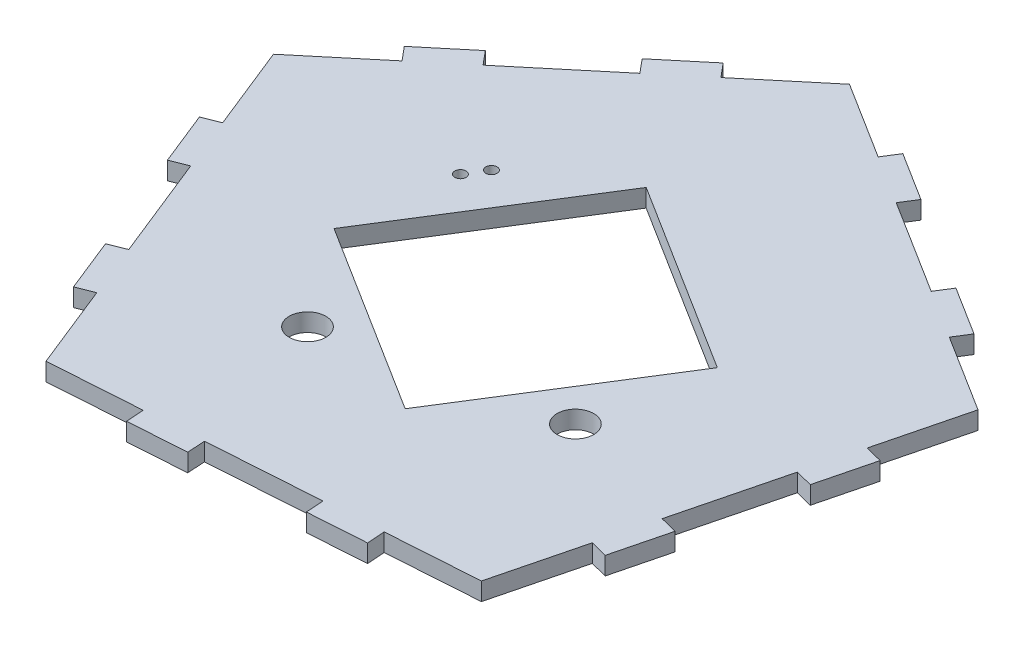
SolidWorks part; units mm, degrees
ref_plane "Front Plane" through (0, 0, 0) normal (0, 0, 1) x (1, 0, 0)
ref_plane "Top Plane" through (0, 0, 0) normal (0, 1, 0) x (1, 0, 0)
ref_plane "Right Plane" through (0, 0, 0) normal (1, 0, 0) x (0, 0, -1)
sketch "Sketch1" plane through (0, 0, 0) normal (0, 1, 0) x (1, 0, 0)
  line L1 (-59.9258, 15.1181) -> (-32.8962, -52.3211)
  line L2 (-32.8962, -52.3211) -> (39.5948, -47.4543)
  line L3 (39.5948, -47.4543) -> (57.3672, 22.9927)
  line L4 (57.3672, 22.9927) -> (-4.14, 61.6646)
  line L5 (-4.14, 61.6646) -> (-59.9258, 15.1181)
  circle A0 centre (0, 0) radius 50 construction
  dimension "D1" = 100
extrude "Boss-Extrude1" add sketch "Sketch1" along normal blind 3.18
ref_axis "Axis" through (0, 3.339, 0) along (0, -1, 0)
sketch "Axis Check" plane through (0, 3.18, 0) normal (0, 1, 0) x (1, 0, 0)
  line L0 (3.3493, -49.8877) -> (-4.14, 61.6646) construction
  line L1 (-32.8962, -52.3211) -> (39.5948, -47.4543) construction
  line L2 (57.3672, 22.9927) -> (-46.411, -18.6015) construction
  line L3 (-59.9258, 15.1181) -> (-32.8962, -52.3211) construction
  line L4 (-32.0329, 38.3913) -> (39.5948, -47.4543) construction
  line L5 (-4.14, 61.6646) -> (-59.9258, 15.1181) construction
  line L6 (-59.9258, 15.1181) -> (48.481, -12.2308) construction
  line L7 (39.5948, -47.4543) -> (57.3672, 22.9927) construction
  line L8 (-32.8962, -52.3211) -> (26.6136, 42.3287) construction
  line L9 (57.3672, 22.9927) -> (-4.14, 61.6646) construction
sketch "Sketch2" plane through (0, 0, 0) normal (0, -1, 0) x (1, 0, 0)
  line L0 (-53.8107, 0.1392) -> (-50.859, -1.0438)
  line L1 (-53.8107, 0.1392) -> (-50.1723, 9.2172)
  line L2 (-50.859, -1.0438) -> (-47.2205, 8.0342)
  line L3 (-50.1723, 9.2172) -> (-47.2205, 8.0342)
  line L4 (-59.9258, -15.1181) -> (-32.8962, 52.3211) construction
  line L5 (-42.6498, 27.9858) -> (-39.0113, 37.0638)
  line L6 (-42.6498, 27.9858) -> (-39.6981, 26.8028)
  line L7 (-39.0113, 37.0638) -> (-36.0596, 35.8808)
  line L8 (-39.6981, 26.8028) -> (-36.0596, 35.8808)
  line L9 (-46.411, 18.6015) -> (-19.2439, 7.7129) construction
  line L10 (-40.8306, 32.5248) -> (-37.8788, 31.3418) construction
  dimension "D1" = 3.18
  dimension "D2" = 9.78
  dimension "D3" = 10.11
extrude "Cut F" [suppressed] cut sketch "Sketch2" against normal through all
sketch "Sketch4" plane through (0, 3.18, 0) normal (0, 1, 0) x (1, 0, 0)
  line L9 (26.6136, 42.3287) -> (-26.6136, -42.3287) construction
  line L10 (57.3672, 22.9927) -> (-4.14, 61.6646) construction
  line L11 (-27.7286, -6.3206) -> (-6.3206, 27.7286)
  line L12 (-27.7286, -6.3206) -> (6.3206, -27.7286)
  line L13 (-6.3206, 27.7286) -> (27.7286, 6.3206)
  line L14 (6.3206, -27.7286) -> (27.7286, 6.3206)
  line L15 (-27.7286, -6.3206) -> (27.7286, 6.3206) construction
  line L16 (-6.3206, 27.7286) -> (6.3206, -27.7286) construction
  line L20 (0, 0) -> (39.0006, -24.5211) construction
  circle A0 centre (-14.9622, -23.7972) radius 3.25
  circle A1 centre (23.7972, -14.9622) radius 3.25
  point P5 (0, 0)
  point P6 (-14.9622, -23.7972)
  dimension "D3" = 6.5
  dimension "D1" = 40.22
  dimension "D2" = 40.22
  dimension "D4" = 8
  dimension "D5" = 8
extrude "Top Cut" cut sketch "Sketch4" against normal blind 10
sketch "Sketch7" plane through (0, 3.18, 0) normal (0, 1, 0) x (1, 0, 0)
  line L0 (0, 0) -> (26.6136, 42.3287) construction
  line L1 (57.3672, 22.9927) -> (-4.14, 61.6646) construction
  line L2 (1.0645, 1.6931) -> (-22.7326, 16.6553) construction
  line L3 (-6.1086, 1.4782) -> (-24.8617, 13.269) construction
  line L5 (-6.3206, 27.7286) -> (-27.7286, -6.3206) construction
  circle A0 centre (-22.7326, 16.6553) radius 1
  circle A1 centre (-24.8617, 13.269) radius 1
  dimension "D5" = 2
  dimension "D1" = 4
  dimension "D2" = 2
  dimension "D3" = 8
  dimension "D4" = 8
extrude "Top Cut 2" cut sketch "Sketch7" against normal through all
sketch "Sketch8" [suppressed] plane through (0, 3.18, 0) normal (0, 1, 0) x (1, 0, 0)
  line L0 (3.3493, -49.8877) -> (-4.14, 61.6646) construction
  line L5 (-32.8962, -52.3211) -> (39.5948, -47.4543) construction
  line L6 (-17.9455, -31.2723) -> (21.9647, -28.5929)
  line L11 (-17.9455, -31.2723) -> (-21.9647, 28.5929)
  line L12 (21.9647, -28.5929) -> (17.9455, 31.2723)
  line L13 (-21.9647, 28.5929) -> (17.9455, 31.2723)
  point P4 (1.4955, -22.2759)
  dimension "D1" = 60
  dimension "D2" = 40
  dimension "D3" = 20
extrude "Bottom Cut" [suppressed] cut sketch "Sketch8" against normal blind 10
sketch "Sketch9" [suppressed] plane through (0, 3.18, 0) normal (0, 1, 0) x (1, 0, 0)
  line L0 (19.9551, 1.3397) -> (-19.9551, -1.3397) construction
  line L1 (21.9647, -28.5929) -> (17.9455, 31.2723) construction
  line L2 (-21.9647, 28.5929) -> (-17.9455, -31.2723) construction
  line L3 (-19.9551, -1.3397) -> (-44.4689, -2.9855) construction
  line L4 (19.9551, 1.3397) -> (43.083, 2.8925) construction
  line L5 (-32.8962, -52.3211) -> (39.5948, -47.4543) construction
  line L6 (-29.6051, -6.8886) -> (-32.7779, -7.1016)
  line L7 (-29.6051, -6.8886) -> (-30.2602, 2.8694)
  line L8 (-30.2602, 2.8694) -> (-33.433, 2.6564)
  line L9 (-32.7779, -7.1016) -> (-33.433, 2.6564)
  line L10 (-29.6051, -6.8886) -> (-33.433, 2.6564) construction
  line L11 (-30.2602, 2.8694) -> (-32.7779, -7.1016) construction
  line L12 (33.433, -2.6564) -> (30.2602, -2.8694)
  line L13 (33.433, -2.6564) -> (32.7779, 7.1016)
  line L14 (32.7779, 7.1016) -> (29.6051, 6.8886)
  line L15 (30.2602, -2.8694) -> (29.6051, 6.8886)
  line L16 (33.433, -2.6564) -> (29.6051, 6.8886) construction
  line L17 (32.7779, 7.1016) -> (30.2602, -2.8694) construction
  line L18 (-32.8962, -52.3211) -> (39.5948, -47.4543) construction
  point P6 (-31.519, -2.1161)
  point P13 (31.519, 2.1161)
  dimension "D1" = 9.78
  dimension "D2" = 3.18
  dimension "D3" = 3.18
  dimension "D4" = 9.78
  dimension "D5" = 10
  dimension "D6" = 10
extrude "Battery Holder Cut" [suppressed] cut sketch "Sketch9" against normal blind 3.18
sketch "Sketch3" plane through (0, 3.18, 0) normal (0, 1, 0) x (1, 0, 0)
  line L0 (0, 0) -> (-40.9819, 49.1167) construction
  line L1 (-49.5112, 27.9494) -> (-45.4366, 23.066)
  line L3 (-45.4366, 23.066) -> (-37.5894, 29.6135)
  line L4 (-41.664, 34.4969) -> (-37.5894, 29.6135)
  line L5 (-4.14, 61.6646) -> (-59.9258, 15.1181) construction
  line L6 (-71.9961, 5.0469) -> (-69.9588, 2.6052)
  line L7 (-71.9961, 5.0469) -> (-47.4739, 25.5077)
  line L14 (-26.4764, 47.1691) -> (-22.4018, 42.2857)
  line L16 (-22.4018, 42.2857) -> (-14.5546, 48.8333)
  line L17 (-18.6292, 53.7166) -> (-14.5546, 48.8333)
  line L18 (-42.539, 27.5695) -> (-41.513, 26.3398) construction
  line L19 (-49.5112, 27.9494) -> (-41.664, 34.4969)
  line L21 (-26.4764, 47.1691) -> (-18.6292, 53.7166)
  line L22 (-16.5919, 51.275) -> (4.7866, 69.1127)
  line L23 (-39.6267, 32.0552) -> (-24.4391, 44.7274)
  line M18 (-4.14, 61.6646) -> (-59.9258, 15.1181)
  dimension "D1" = 3.18
  dimension "D2" = 10.22
  dimension "D3" = 9.89
  dimension "D4" = 100
extrude "Extrude M" add sketch "Sketch3" against normal up to surface (3.18 mm away) contours L21 L14 L7 L17 | L19 L1 L4 M18 region at (-44.5689, 3.18, -30.0023) region at (-21.5341, 3.18, -49.222) up to face at (-22.7326, 0, -15.6553)
pattern_circular "Circle F" [suppressed] count 5 over 360 about axis through (0, 3.339, 0) along (0, -1, 0) of bodies 173
pattern_circular "Circle M" count 5 over 360 about axis through (0, 3.339, 0) along (0, -1, 0) of "Extrude M"
pattern_circular "Circle Side F" [suppressed] count 5 over 360 about axis through (0, 3.339, 0) along (0, -1, 0) of bodies 173
pattern_circular "Circle Side M" [suppressed] count 5 over 360 about axis through (0, 3.339, 0) along (0, -1, 0) of bodies 168
equation "\"kerf\"= .22mm"
equation "\"tabWidthF\"= 10 - \"kerf\""
equation "\"tabThickness\"= 3.18"
equation "\"D1@Sketch2\"=\"tabThickness\""
equation "\"tabWidthM\"= 10 + \"kerf\""
equation "\"halfkerf\"= \"kerf\" / 2.00mm"
equation "\"D1@Sketch9\"=\"tabWidthF\""
equation "\"D2@Sketch9\"=\"tabThickness\""
equation "\"D3@Sketch9\"=\"tabThickness\""
equation "\"D4@Sketch9\"=\"tabWidthF\""
equation "\"D1@Battery Holder Cut\"=\"tabThickness\""
equation "\"tabLength\" = \"kerf\" + 12"
